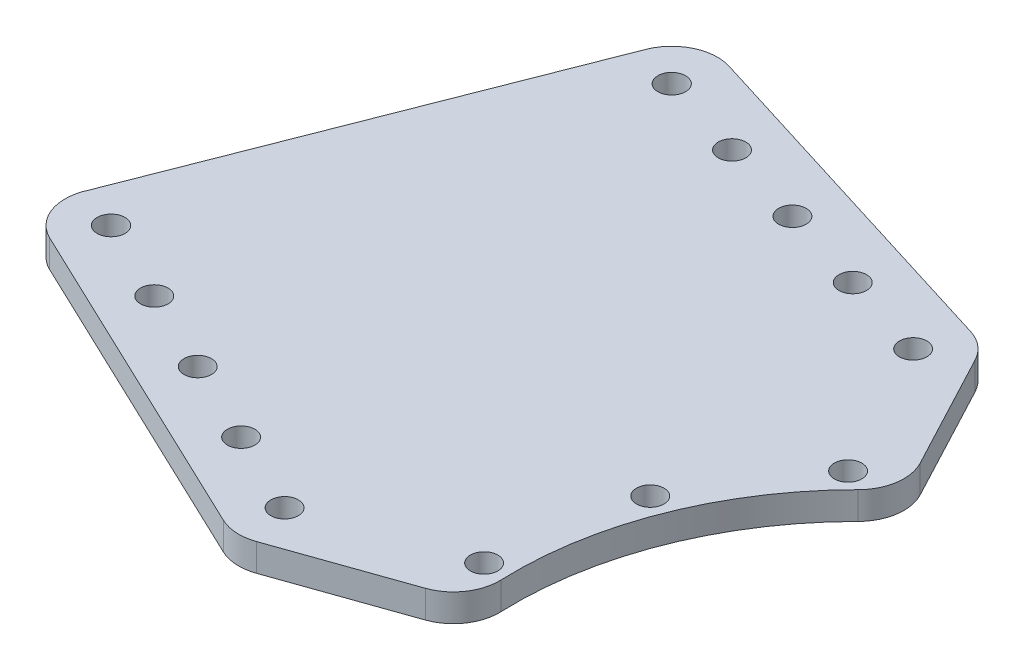
SolidWorks part; units mm, degrees
ref_plane "前视基准面" through (0, 0, 0) normal (0, 0, 1) x (1, 0, 0)
ref_plane "上视基准面" through (0, 0, 0) normal (0, 1, 0) x (1, 0, 0)
ref_plane "右视基准面" through (0, 0, 0) normal (1, 0, 0) x (0, 0, -1)
other "Configuration Table"
sketch "草图2" plane through (0, -17.3959, 0) normal (0, 1, 0) x (1, 0, 0)
  line L1 (-67.7502, -36.977) -> (-103.859, -19.7974)
  line L3 (-106.2324, -13.116) -> (-89.1855, 30.4759)
  line L4 (-83.0443, 33.4294) -> (-44.8604, 21.5564)
  line L5 (-41.9259, 19.121) -> (-35.1765, 6.3696)
  line L6 (-50.333, -32.3883) -> (-63.942, -37.1784)
  arc A0 (-103.859, -19.7974) -> (-106.2324, -13.116) centre (-101.7049, -15.27) cw
  arc A1 (-89.1855, 30.4759) -> (-83.0443, 33.4294) centre (-84.5289, 28.6549) cw
  arc A2 (-44.8604, 21.5564) -> (-41.9259, 19.121) centre (-46.345, 16.7819) cw
  arc A3 (-35.1765, 6.3696) -> (-36.058, 0.4971) centre (-39.5956, 4.0306) cw
  arc A4 (-36.058, 0.4971) -> (-46.9969, -27.4757) centre (-9.5258, -26.0037) ccw
  arc A5 (-46.9969, -27.4757) -> (-50.333, -32.3883) centre (-51.993, -27.6719) cw
  arc A6 (-63.942, -37.1784) -> (-67.7502, -36.977) centre (-65.6021, -32.462) cw
  circle A7 centre (-65.6021, -32.462) radius 1.5
  circle A8 centre (-74.6321, -28.1657) radius 1.5
  circle A9 centre (-83.6622, -23.8695) radius 1.5
  circle A10 centre (-92.6923, -19.5732) radius 1.5
  circle A11 centre (-101.7049, -15.27) radius 1.5187
  circle A12 centre (-84.5289, 28.6549) radius 1.5127
  circle A13 centre (-74.9921, 25.6895) radius 1.5
  circle A14 centre (-65.443, 22.7203) radius 1.5
  circle A15 centre (-55.894, 19.7511) radius 1.5
  circle A16 centre (-46.345, 16.7819) radius 1.5
  circle A17 centre (-38.368, 1.7114) radius 1.5
  circle A18 centre (-46.7787, -11.4358) radius 1.5
  circle A19 centre (-49.5179, -26.8007) radius 1.5
extrude "凸台-拉伸1" add sketch "草图2" along normal blind 3
